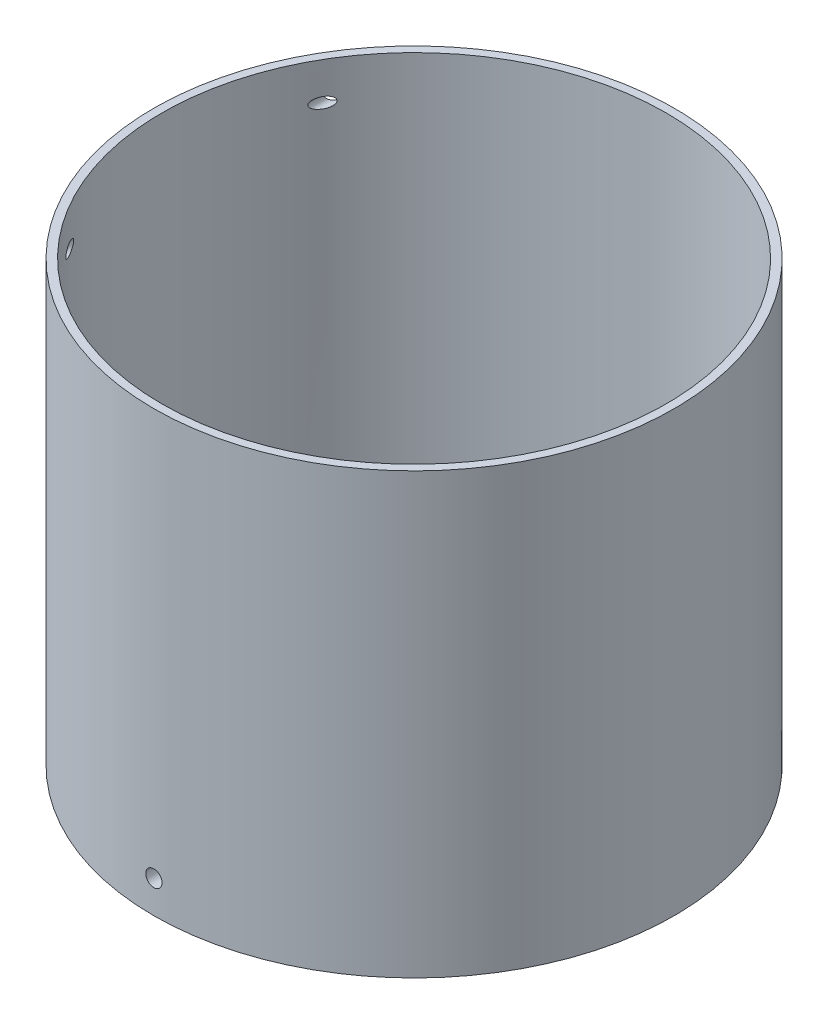
SolidWorks part; units mm, degrees
material "6061-T6 (SS)"
ref_plane "Front Plane" through (0, 0, 0) normal (0, 0, 1) x (1, 0, 0)
ref_plane "Top Plane" through (0, 0, 0) normal (0, 1, 0) x (1, 0, 0)
ref_plane "Right Plane" through (0, 0, 0) normal (1, 0, 0) x (0, 0, -1)
sketch "Sketch1" plane through (0, 0, 0) normal (0, 1, 0) x (1, 0, 0)
  circle A0 centre (0, 0) radius 101.6
  circle A1 centre (0, 0) radius 95.25
  dimension "D1" = 203.2
  dimension "D2" = 190.5
extrude "Boss-Extrude1" add sketch "Sketch1" along normal blind 25.4
sketch "Sketch2" plane through (0, 0, 0) normal (0, 0, 1) x (1, 0, 0)
  circle A0 centre (0, 12.7) radius 3.175
  dimension "D1" = 6.35
extrude "Cut-Extrude1" cut sketch "Sketch2" against normal through all and the other way through all
sketch "Sketch3" plane through (0, 0, 0) normal (1, 0, 0) x (0, 0, -1)
  circle A0 centre (0, 12.7) radius 1.5875
  dimension "D1" = 3.175
extrude "Cut-Extrude3" [suppressed] cut sketch "Sketch3" against normal through all
sketch "Sketch4" plane through (0, 0, 0) normal (1, 0, 0) x (0, 0, -1)
  line L0 (0, 0) -> (0, 72.5565) construction
pattern_circular "CirPattern1" [suppressed] count 24 over 360 about axis through (0, 0, 0) along (0, 1, 0) reverse direction yes of bodies 103
sketch "Sketch5" plane through (0, 25.4, 0) normal (0, 1, 0) x (1, 0, 0)
  circle A0 centre (0, 0) radius 98.425
  circle A1 centre (0, 0) radius 101.6
extrude "Boss-Extrude2" add sketch "Sketch5" along normal blind 146.05
sketch "Sketch6" plane through (0, 0, 0) normal (0, -1, 0) x (1, 0, 0)
  circle A0 centre (0, 0) radius 101.6
  circle A1 centre (0, 0) radius 98.425
extrude "Boss-Extrude3" [suppressed] add sketch "Sketch6" along normal blind 133.35
ref_plane "Plane1" through (0, 0, 101.6) normal (0, 0, 1) x (1, 0, 0)
sketch "Sketch9" plane through (0, 0, 101.6) normal (0, 0, 1) x (1, 0, 0)
  line L0 (-101.6, 0) -> (101.6, 0) construction
  line L1 (0, 0) -> (0, 72.5565) construction
  circle A0 centre (-85.075, 156.8) radius 2.1
  dimension "D1" = 156.8
  dimension "D2" = 85.075
extrude "Cut-Extrude5" cut sketch "Sketch9" against normal through all
